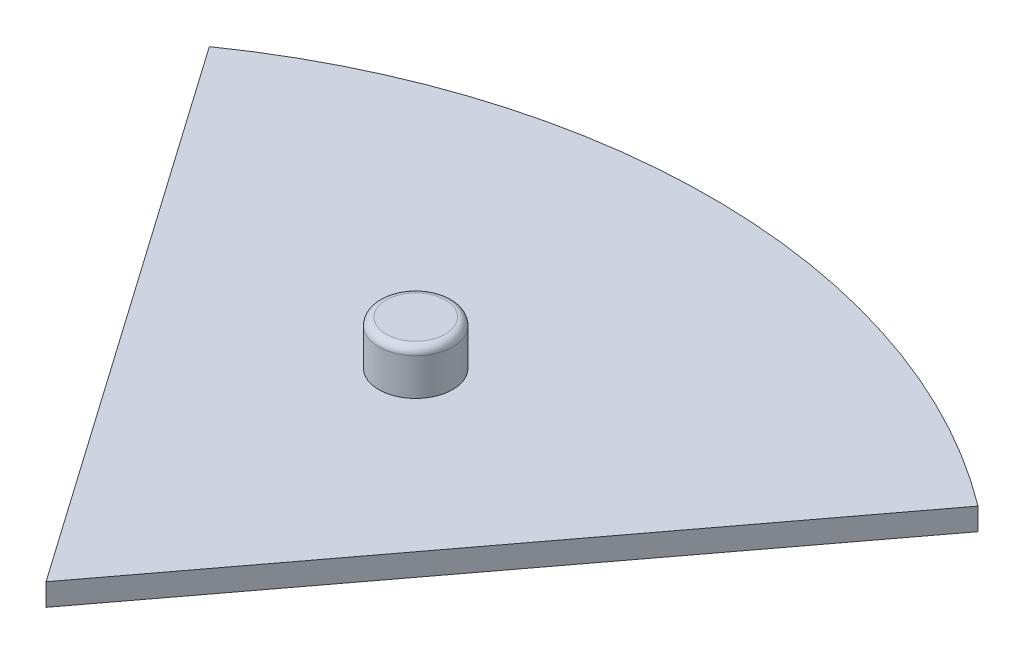
SolidWorks part; units mm, degrees
ref_plane "Front Plane" through (0, 0, 0) normal (0, 0, 1) x (1, 0, 0)
ref_plane "Top Plane" through (0, 0, 0) normal (0, 1, 0) x (1, 0, 0)
ref_plane "Right Plane" through (0, 0, 0) normal (1, 0, 0) x (0, 0, -1)
sketch "Sketch2" plane through (0, 0, 0) normal (0, 1, 0) x (1, 0, 0)
  line L1 (0, 0) -> (-25.8151, 36.8589)
  line L3 (0, 0) -> (27.0776, 35.9416)
  line L4 (0, 0) -> (42.55, -14.6458)
  line L5 (0, 0) -> (-0.7803, -44.9932)
  line L6 (0, 0) -> (-43.0322, -13.1615)
  circle A0 centre (0, 0) radius 45
  point P10 (0, 0)
  point P16 (0, 0)
  dimension "D1" = 5
extrude "Boss-Extrude1" add sketch "Sketch2" along normal blind 1.5 contours L3 A0 L1 region at (0.4867, 0, -28.0605)
sketch "Sketch3" plane through (0, 0, 0) normal (0, -1, 0) x (1, 0, 0)
  line L0 (0, 0) -> (0, -35)
  line L1 (0, -35) -> (10, -35) construction
  line L2 (0, -34.375) -> (10, -34.375)
  line L3 (0, -35.625) -> (10, -35.625)
  arc A0 (0, -34.375) -> (0, -35.625) centre (0, -35) ccw
  arc A1 (10, -35.625) -> (10, -34.375) centre (10, -35) ccw
  point P3 (5, -35)
extrude "Boss-Extrude2" add sketch "Sketch3" along normal blind 1.5 contours L2 A1 L3 A0
sketch "Sketch4" plane through (0, 1.5, 0) normal (0, 1, 0) x (1, 0, 0)
  line L0 (0, 0) -> (0, 25)
  circle A0 centre (0, 25) radius 2.5
extrude "Boss-Extrude3" add sketch "Sketch4" along normal blind 3 contours A0 region at (1.7178, 1.5, -23.2822)
fillet "Fillet1" radius 0.5 1 edges at (0, 4.5, -22.5)
